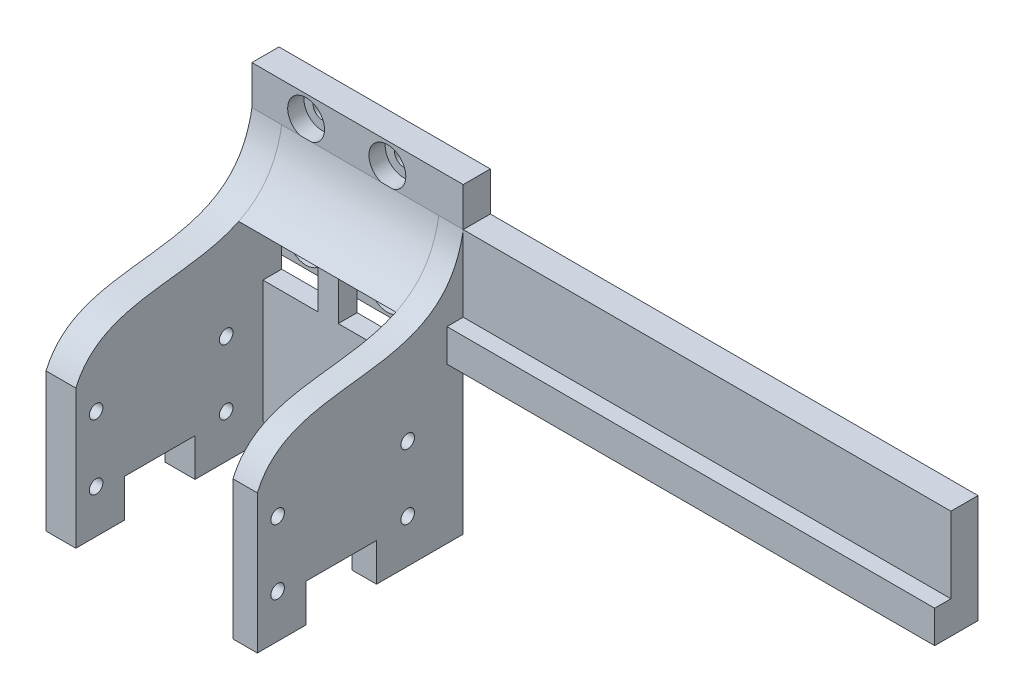
SolidWorks part; units mm, degrees
ref_plane "Front Plane" through (0, 0, 0) normal (0, 0, 1) x (1, 0, 0)
ref_plane "Top Plane" through (0, 0, 0) normal (0, 1, 0) x (1, 0, 0)
ref_plane "Right Plane" through (0, 0, 0) normal (1, 0, 0) x (0, 0, -1)
sketch "Sketch1" plane through (0, 0, 0) normal (0, 0, 1) x (1, 0, 0)
  line L0 (-17.7547, -9.0498) -> (-17.7547, -1.8498)
  line L1 (-56.7547, -1.8498) -> (-17.7547, -1.8498)
  line L2 (-56.7547, -1.8498) -> (-56.7547, -15.4856)
  line L3 (-17.7547, -29.0498) -> (72.2453, -29.0498)
  line L4 (72.2453, -9.0498) -> (72.2453, -29.0498)
  line L5 (-17.7547, -9.0498) -> (72.2453, -9.0498)
  line L8 (-56.7547, -15.4856) -> (-56.7547, -29.8498)
  line L9 (-56.7547, -29.8498) -> (-17.7547, -29.8498)
  line L10 (-17.7547, -29.0498) -> (-17.7547, -29.8498)
  point P0 (0, 0)
  dimension "D1" = 7.2
  dimension "D2" = 20
  dimension "D3" = 90
  dimension "D4" = 39
  dimension "D5" = 39
extrude "Boss-Extrude1" add sketch "Sketch1" along normal blind 5
sketch "Sketch2" plane through (0, 0, 5) normal (0, 0, 1) x (1, 0, 0)
  line L0 (-46.7547, -5.8498) -> (-46.7547, -25.8498) construction
  line L1 (-46.7547, -25.8498) -> (-31.7547, -25.8498) construction
  line L2 (-31.7547, -25.8498) -> (-31.7547, -5.8498) construction
  line L3 (-31.7547, -5.8498) -> (-46.7547, -5.8498) construction
  line L4 (-56.7547, -29.8498) -> (-17.7547, -29.8498) construction
  line L5 (-56.7547, -1.8498) -> (-56.7547, -29.8498) construction
  line L6 (-46.7547, -5.8498) -> (-31.7547, -25.8498) construction
  line L7 (-31.7547, -5.8498) -> (-46.7547, -25.8498) construction
  line L8 (-39.2547, -15.8498) -> (72.2453, -15.8498) construction
  line L9 (72.2453, -29.0498) -> (72.2453, -9.0498) construction
  line L10 (-17.7547, -1.8498) -> (-56.7547, -1.8498) construction
  circle A0 centre (-46.7547, -5.8498) radius 1.7
  circle A1 centre (-31.7547, -5.8498) radius 1.7
  circle A2 centre (-31.7547, -25.8498) radius 1.7
  circle A3 centre (-46.7547, -25.8498) radius 1.7
  point P12 (-37.2547, -29.8498)
  dimension "D1" = 3.4
  dimension "D2" = 15
  dimension "D3" = 20
  dimension "D4" = 15
  dimension "D5" = 20
  dimension "D6" = 4
  dimension "D7" = 10
  dimension "D8" = 14
extrude "Cut-Extrude1" cut sketch "Sketch2" against normal up to surface (5 mm away) contours A1 | A0 | A3 | A2 up to face at (-5.0047, -17.4498, 0)
sketch "Sketch3" plane through (0, 0, 5) normal (0, 0, 1) x (1, 0, 0)
  line L0 (-56.7547, -1.8498) -> (-56.7547, -29.8498) construction
  line L1 (-56.7547, -11.8498) -> (-51.2547, -11.8498)
  line L2 (-56.7547, -11.8498) -> (-56.7547, -57.7298)
  line L3 (-56.7547, -57.7298) -> (-51.2547, -57.7298)
  line L4 (-51.2547, -11.8498) -> (-51.2547, -57.7298)
  line L6 (-17.7547, -29.8498) -> (-17.7547, -29.0498) construction
  line L7 (-17.7547, -57.7298) -> (-22.2547, -57.7298)
  line L8 (-17.7547, -57.7298) -> (-17.7547, -11.8498)
  line L9 (-17.7547, -11.8498) -> (-22.2547, -11.8498)
  line L10 (-22.2547, -57.7298) -> (-22.2547, -11.8498)
  line L11 (-17.7547, -1.8498) -> (-56.7547, -1.8498) construction
  line L12 (-56.7547, -29.8498) -> (-17.7547, -29.8498) construction
  dimension "D1" = 27.88
  dimension "D2" = 27.88
  dimension "D3" = 29
  dimension "D4" = 4.5
  dimension "D5" = 0
  dimension "D6" = 0
  dimension "D7" = 10
extrude "Boss-Extrude2" add sketch "Sketch3" along normal blind 38
sketch "Sketch4" plane through (-56.7547, 0, 0) normal (-1, 0, 0) x (0, 0, 1)
  line L0 (5, -29.8498) -> (0, -29.8498) construction
  line L5 (34, -57.7298) -> (34, -50.7298)
  line L6 (34, -50.7298) -> (21, -50.7298)
  line L7 (21, -50.7298) -> (21, -57.7298)
  line L8 (15.25, -37.7298) -> (15.25, -49.7298) construction
  line L9 (15.25, -49.7298) -> (39.25, -49.7298) construction
  line L10 (39.25, -49.7298) -> (39.25, -37.7298) construction
  line L11 (43, -57.7298) -> (5, -57.7298) construction
  line L14 (2.5, -29.8498) -> (8, -29.8498)
  line L15 (2.5, -29.8498) -> (2.5, -61.3623)
  line L16 (2.5, -61.3623) -> (8, -61.3623)
  line L18 (21, -57.7298) -> (34, -57.7298)
  line L23 (39.25, -37.7298) -> (15.25, -37.7298) construction
  line L24 (8, -29.8498) -> (8, -61.3623)
  line L25 (5, -29.8498) -> (5, -57.7298) construction
  circle A0 centre (15.25, -37.7298) radius 1.25
  circle A1 centre (39.25, -37.7298) radius 1.25
  circle A2 centre (39.25, -49.7298) radius 1.25
  circle A3 centre (15.25, -49.7298) radius 1.25
  line M2 (0, -29.8498) -> (5, -29.8498)
  dimension "D1" = 12
  dimension "D6" = 2.5
  dimension "D3" = 24
  dimension "D4" = 7
  dimension "D5" = 13
  dimension "D7" = 8
  dimension "D8" = 3
  dimension "D9" = 7.25
  dimension "D10" = 13
  dimension "D2" = 0
extrude "Cut-Extrude2" cut sketch "Sketch4" against normal up to surface (39 mm away) contours A0 | A1 | A2 | L6 L7 L5 M2 | A3 region at (-56.7547, -54.2298, 27.5) region at (-56.7547, -37.7298, 15.25) region at (-56.7547, -37.7298, 39.25) region at (-56.7547, -49.7298, 39.25) region at (-56.7547, -49.7298, 15.25) up to face at (-17.7547, -32.1198, 13.25)
sketch "Sketch5" plane through (0, 0, 0) normal (0, 0, -1) x (-1, 0, 0)
  line L0 (-72.2453, -29.0498) -> (-7.1104, -29.0498) construction
  line L2 (-72.2453, -26.6698) -> (-71.8003, -26.6698) construction
  line L3 (-65.5853, -26.6698) -> (-65.1403, -26.6698)
  line L4 (-72.2453, -29.0498) -> (-72.2453, -9.0498) construction
  line L5 (-72.2453, -26.6698) -> (-71.8003, -26.6698)
  line L6 (-71.8003, -26.6698) -> (-70.9844, -28.9116)
  line L7 (-70.787, -29.0498) -> (-70.377, -29.0498)
  line L8 (-70.1797, -28.9116) -> (-69.3637, -26.6698)
  line L9 (-69.3637, -26.6698) -> (-68.4737, -26.6698)
  line L10 (-68.4737, -26.6698) -> (-67.6578, -28.9116)
  line L11 (-67.4604, -29.0498) -> (-67.0504, -29.0498)
  line L12 (-66.8531, -28.9116) -> (-66.0372, -26.6698)
  line L13 (-66.0372, -26.6698) -> (-65.5872, -26.6698)
  line L14 (-65.1403, -26.6698) -> (-64.3244, -28.9116)
  line L15 (-64.127, -29.0498) -> (-63.717, -29.0498)
  line L16 (-63.5197, -28.9116) -> (-62.7037, -26.6698)
  line L17 (-62.7037, -26.6698) -> (-61.8137, -26.6698)
  line L18 (-61.8137, -26.6698) -> (-60.9978, -28.9116)
  line L19 (-60.8004, -29.0498) -> (-60.3904, -29.0498)
  line L20 (-60.1931, -28.9116) -> (-59.3772, -26.6698)
  line L21 (-59.3772, -26.6698) -> (-58.9272, -26.6698)
  line L22 (-58.9253, -26.6698) -> (-58.4803, -26.6698)
  line L23 (-58.4803, -26.6698) -> (-57.6644, -28.9116)
  line L24 (-57.467, -29.0498) -> (-57.057, -29.0498)
  line L25 (-56.8597, -28.9116) -> (-56.0437, -26.6698)
  line L26 (-56.0437, -26.6698) -> (-55.1537, -26.6698)
  line L27 (-55.1537, -26.6698) -> (-54.3378, -28.9116)
  line L28 (-54.1404, -29.0498) -> (-53.7304, -29.0498)
  line L29 (-53.5331, -28.9116) -> (-52.7172, -26.6698)
  line L30 (-52.7172, -26.6698) -> (-52.2672, -26.6698)
  line L31 (-52.2653, -26.6698) -> (-51.8203, -26.6698)
  line L32 (-51.8203, -26.6698) -> (-51.0044, -28.9116)
  line L33 (-50.807, -29.0498) -> (-50.397, -29.0498)
  line L34 (-50.1997, -28.9116) -> (-49.3837, -26.6698)
  line L35 (-49.3837, -26.6698) -> (-48.4937, -26.6698)
  line L36 (-48.4937, -26.6698) -> (-47.6778, -28.9116)
  line L37 (-47.4804, -29.0498) -> (-47.0704, -29.0498)
  line L38 (-46.8731, -28.9116) -> (-46.0572, -26.6698)
  line L39 (-46.0572, -26.6698) -> (-45.6072, -26.6698)
  line L40 (-45.6053, -26.6698) -> (-45.1603, -26.6698)
  line L41 (-45.1603, -26.6698) -> (-44.3444, -28.9116)
  line L42 (-44.147, -29.0498) -> (-43.737, -29.0498)
  line L43 (-43.5397, -28.9116) -> (-42.7237, -26.6698)
  line L44 (-42.7237, -26.6698) -> (-41.8337, -26.6698)
  line L45 (-41.8337, -26.6698) -> (-41.0178, -28.9116)
  line L46 (-40.8204, -29.0498) -> (-40.4104, -29.0498)
  line L47 (-40.2131, -28.9116) -> (-39.3972, -26.6698)
  line L48 (-39.3972, -26.6698) -> (-38.9472, -26.6698)
  line L49 (-38.9453, -26.6698) -> (-38.5003, -26.6698)
  line L50 (-38.5003, -26.6698) -> (-37.6844, -28.9116)
  line L51 (-37.487, -29.0498) -> (-37.077, -29.0498)
  line L52 (-36.8797, -28.9116) -> (-36.0637, -26.6698)
  line L53 (-36.0637, -26.6698) -> (-35.1737, -26.6698)
  line L54 (-35.1737, -26.6698) -> (-34.3578, -28.9116)
  line L55 (-34.1604, -29.0498) -> (-33.7504, -29.0498)
  line L56 (-33.5531, -28.9116) -> (-32.7372, -26.6698)
  line L57 (-32.7372, -26.6698) -> (-32.2872, -26.6698)
  line L58 (-32.2853, -26.6698) -> (-31.8403, -26.6698)
  line L59 (-31.8403, -26.6698) -> (-31.0244, -28.9116)
  line L60 (-30.827, -29.0498) -> (-30.417, -29.0498)
  line L61 (-30.2197, -28.9116) -> (-29.4037, -26.6698)
  line L62 (-29.4037, -26.6698) -> (-28.5137, -26.6698)
  line L63 (-28.5137, -26.6698) -> (-27.6978, -28.9116)
  line L64 (-27.5004, -29.0498) -> (-27.0904, -29.0498)
  line L65 (-26.8931, -28.9116) -> (-26.0772, -26.6698)
  line L66 (-26.0772, -26.6698) -> (-25.6272, -26.6698)
  line L67 (-25.6253, -26.6698) -> (-25.1803, -26.6698)
  line L68 (-25.1803, -26.6698) -> (-24.3644, -28.9116)
  line L69 (-24.167, -29.0498) -> (-23.757, -29.0498)
  line L70 (-23.5597, -28.9116) -> (-22.7437, -26.6698)
  line L71 (-22.7437, -26.6698) -> (-21.8537, -26.6698)
  line L72 (-21.8537, -26.6698) -> (-21.0378, -28.9116)
  line L73 (-20.8404, -29.0498) -> (-20.4304, -29.0498)
  line L74 (-20.2331, -28.9116) -> (-19.4172, -26.6698)
  line L75 (-19.4172, -26.6698) -> (-18.9672, -26.6698)
  line L76 (-18.9653, -26.6698) -> (-18.5203, -26.6698)
  line L77 (-18.5203, -26.6698) -> (-17.7044, -28.9116)
  line L78 (-17.507, -29.0498) -> (-17.097, -29.0498)
  line L79 (-16.8997, -28.9116) -> (-16.0837, -26.6698)
  line L80 (-16.0837, -26.6698) -> (-15.1937, -26.6698)
  line L81 (-15.1937, -26.6698) -> (-14.3778, -28.9116)
  line L82 (-14.1804, -29.0498) -> (-13.7704, -29.0498)
  line L83 (-13.5731, -28.9116) -> (-12.7572, -26.6698)
  line L84 (-12.7572, -26.6698) -> (-12.3072, -26.6698)
  line L85 (-12.3053, -26.6698) -> (-11.8603, -26.6698)
  line L86 (-11.8603, -26.6698) -> (-11.0444, -28.9116)
  line L87 (-10.847, -29.0498) -> (-10.437, -29.0498)
  line L88 (-10.2397, -28.9116) -> (-9.4237, -26.6698)
  line L89 (-9.4237, -26.6698) -> (-8.5337, -26.6698)
  line L90 (-8.5337, -26.6698) -> (-7.7178, -28.9116)
  line L91 (-7.5204, -29.0498) -> (-7.1104, -29.0498)
  line L92 (-6.9131, -28.9116) -> (-6.0972, -26.6698)
  line L93 (-6.0972, -26.6698) -> (-5.6472, -26.6698)
  line L94 (-69.3637, -26.6698) -> (-68.4737, -26.6698) construction
  line L95 (-72.2453, -25.6698) -> (-5.6472, -25.6698)
  line L96 (-72.2453, -25.6698) -> (-72.2453, -26.6698)
  line L97 (-72.2453, -26.6698) -> (-71.8003, -26.6698)
  line L98 (-5.6472, -25.6698) -> (-5.6472, -26.6698)
  line L99 (-69.3637, -26.6698) -> (-68.4737, -26.6698)
  line L100 (-66.0372, -26.6698) -> (-65.1403, -26.6698) construction
  line L101 (-66.0372, -26.6698) -> (-65.1403, -26.6698)
  line L102 (-62.7037, -26.6698) -> (-61.8137, -26.6698)
  line L103 (-62.7037, -26.6698) -> (-61.8137, -26.6698) construction
  line L104 (-59.3772, -26.6698) -> (-58.4803, -26.6698)
  line L105 (-59.3772, -26.6698) -> (-58.4803, -26.6698) construction
  line L106 (-56.0437, -26.6698) -> (-55.1537, -26.6698)
  line L107 (-56.0437, -26.6698) -> (-55.1537, -26.6698) construction
  line L108 (-52.7172, -26.6698) -> (-51.8203, -26.6698)
  line L109 (-52.7172, -26.6698) -> (-51.8203, -26.6698) construction
  line L110 (-49.3837, -26.6698) -> (-48.4937, -26.6698) construction
  line L111 (-49.3837, -26.6698) -> (-48.4937, -26.6698)
  line L112 (-46.0572, -26.6698) -> (-45.1603, -26.6698) construction
  line L113 (-46.0572, -26.6698) -> (-45.1603, -26.6698)
  line L114 (-42.7237, -26.6698) -> (-41.8337, -26.6698) construction
  line L115 (-42.7237, -26.6698) -> (-41.8337, -26.6698)
  line L116 (-39.3972, -26.6698) -> (-38.5003, -26.6698) construction
  line L117 (-39.3972, -26.6698) -> (-38.5003, -26.6698)
  line L118 (-36.0637, -26.6698) -> (-35.1737, -26.6698) construction
  line L119 (-36.0637, -26.6698) -> (-35.1737, -26.6698)
  line L120 (-32.7372, -26.6698) -> (-31.8403, -26.6698) construction
  line L121 (-32.7372, -26.6698) -> (-31.8403, -26.6698)
  line L122 (-29.4037, -26.6698) -> (-28.5137, -26.6698) construction
  line L123 (-29.4037, -26.6698) -> (-28.5137, -26.6698)
  line L124 (-26.0772, -26.6698) -> (-25.1803, -26.6698) construction
  line L125 (-26.0772, -26.6698) -> (-25.1803, -26.6698)
  line L126 (-22.7437, -26.6698) -> (-21.8537, -26.6698)
  line L127 (-22.7437, -26.6698) -> (-21.8537, -26.6698) construction
  line L128 (-19.4172, -26.6698) -> (-18.5203, -26.6698)
  line L129 (-19.4172, -26.6698) -> (-18.5203, -26.6698) construction
  line L130 (-16.0837, -26.6698) -> (-15.1937, -26.6698)
  line L131 (-16.0837, -26.6698) -> (-15.1937, -26.6698) construction
  line L132 (-12.7572, -26.6698) -> (-11.8603, -26.6698)
  line L133 (-12.7572, -26.6698) -> (-11.8603, -26.6698) construction
  line L134 (-9.4237, -26.6698) -> (-8.5337, -26.6698)
  line L135 (-9.4237, -26.6698) -> (-8.5337, -26.6698) construction
  line L136 (-6.0972, -26.6698) -> (-5.6472, -26.6698)
  line L137 (-6.0972, -26.6698) -> (-5.6472, -26.6698) construction
  arc A0 (-70.377, -29.0498) -> (-70.1797, -28.9116) centre (-70.377, -28.8398) ccw
  arc A1 (-70.9844, -28.9116) -> (-70.787, -29.0498) centre (-70.787, -28.8398) ccw
  arc A2 (-67.6578, -28.9116) -> (-67.4604, -29.0498) centre (-67.4604, -28.8398) ccw
  arc A3 (-67.0504, -29.0498) -> (-66.8531, -28.9116) centre (-67.0504, -28.8398) ccw
  arc A4 (-63.717, -29.0498) -> (-63.5197, -28.9116) centre (-63.717, -28.8398) ccw
  arc A5 (-64.3244, -28.9116) -> (-64.127, -29.0498) centre (-64.127, -28.8398) ccw
  arc A6 (-60.9978, -28.9116) -> (-60.8004, -29.0498) centre (-60.8004, -28.8398) ccw
  arc A7 (-60.3904, -29.0498) -> (-60.1931, -28.9116) centre (-60.3904, -28.8398) ccw
  arc A8 (-57.057, -29.0498) -> (-56.8597, -28.9116) centre (-57.057, -28.8398) ccw
  arc A9 (-57.6644, -28.9116) -> (-57.467, -29.0498) centre (-57.467, -28.8398) ccw
  arc A10 (-54.3378, -28.9116) -> (-54.1404, -29.0498) centre (-54.1404, -28.8398) ccw
  arc A11 (-53.7304, -29.0498) -> (-53.5331, -28.9116) centre (-53.7304, -28.8398) ccw
  arc A12 (-50.397, -29.0498) -> (-50.1997, -28.9116) centre (-50.397, -28.8398) ccw
  arc A13 (-51.0044, -28.9116) -> (-50.807, -29.0498) centre (-50.807, -28.8398) ccw
  arc A14 (-47.6778, -28.9116) -> (-47.4804, -29.0498) centre (-47.4804, -28.8398) ccw
  arc A15 (-47.0704, -29.0498) -> (-46.8731, -28.9116) centre (-47.0704, -28.8398) ccw
  arc A16 (-43.737, -29.0498) -> (-43.5397, -28.9116) centre (-43.737, -28.8398) ccw
  arc A17 (-44.3444, -28.9116) -> (-44.147, -29.0498) centre (-44.147, -28.8398) ccw
  arc A18 (-41.0178, -28.9116) -> (-40.8204, -29.0498) centre (-40.8204, -28.8398) ccw
  arc A19 (-40.4104, -29.0498) -> (-40.2131, -28.9116) centre (-40.4104, -28.8398) ccw
  arc A20 (-37.077, -29.0498) -> (-36.8797, -28.9116) centre (-37.077, -28.8398) ccw
  arc A21 (-37.6844, -28.9116) -> (-37.487, -29.0498) centre (-37.487, -28.8398) ccw
  arc A22 (-34.3578, -28.9116) -> (-34.1604, -29.0498) centre (-34.1604, -28.8398) ccw
  arc A23 (-33.7504, -29.0498) -> (-33.5531, -28.9116) centre (-33.7504, -28.8398) ccw
  arc A24 (-30.417, -29.0498) -> (-30.2197, -28.9116) centre (-30.417, -28.8398) ccw
  arc A25 (-31.0244, -28.9116) -> (-30.827, -29.0498) centre (-30.827, -28.8398) ccw
  arc A26 (-27.6978, -28.9116) -> (-27.5004, -29.0498) centre (-27.5004, -28.8398) ccw
  arc A27 (-27.0904, -29.0498) -> (-26.8931, -28.9116) centre (-27.0904, -28.8398) ccw
  arc A28 (-23.757, -29.0498) -> (-23.5597, -28.9116) centre (-23.757, -28.8398) ccw
  arc A29 (-24.3644, -28.9116) -> (-24.167, -29.0498) centre (-24.167, -28.8398) ccw
  arc A30 (-21.0378, -28.9116) -> (-20.8404, -29.0498) centre (-20.8404, -28.8398) ccw
  arc A31 (-20.4304, -29.0498) -> (-20.2331, -28.9116) centre (-20.4304, -28.8398) ccw
  arc A32 (-17.097, -29.0498) -> (-16.8997, -28.9116) centre (-17.097, -28.8398) ccw
  arc A33 (-17.7044, -28.9116) -> (-17.507, -29.0498) centre (-17.507, -28.8398) ccw
  arc A34 (-14.3778, -28.9116) -> (-14.1804, -29.0498) centre (-14.1804, -28.8398) ccw
  arc A35 (-13.7704, -29.0498) -> (-13.5731, -28.9116) centre (-13.7704, -28.8398) ccw
  arc A36 (-10.437, -29.0498) -> (-10.2397, -28.9116) centre (-10.437, -28.8398) ccw
  arc A37 (-11.0444, -28.9116) -> (-10.847, -29.0498) centre (-10.847, -28.8398) ccw
  arc A38 (-7.7178, -28.9116) -> (-7.5204, -29.0498) centre (-7.5204, -28.8398) ccw
  arc A39 (-7.1104, -29.0498) -> (-6.9131, -28.9116) centre (-7.1104, -28.8398) ccw
  point P16 (-70.23, -29.0498)
  point P19 (-70.9341, -29.0498)
  point P23 (-67.6075, -29.0498)
  point P28 (-66.9034, -29.0498)
  line M7 (-72.2453, -9.0498) -> (-72.2453, -29.0498)
  line M8 (-72.2453, -29.0498) -> (17.7547, -29.0498)
  dimension "D4" = 0.21
  dimension "D7" = 110
  dimension "D2" = 0.445
  dimension "D5" = 0.21
  dimension "D10" = 0.21
  dimension "D12" = 0.21
  dimension "D1" = 2.38
  dimension "D3" = 0.89
  dimension "D6" = 0.41
  dimension "D8" = 110
  dimension "D9" = 110
  dimension "D11" = 0.41
  dimension "D13" = 0.45
  dimension "D14" = 110
  dimension "D15" = 10
  dimension "D16" = 1
extrude "Boss-Extrude3" add sketch "Sketch5" along normal blind 1 contours L91 A39 L92 L93 L98 L95 L5 L6 A1 A0 L8 L9 L10 A2 A3 L12 L13 L101 L3 L14 A5 A4 L16 L17 L18 A6 A7 L20 L21 L104 L22 L23 A9 A8 L25 L26 L27 A10 A11 L29 L30 L108 L31 L32 M7 M8 region at (65.5862, -26.0029, 0)
sketch "Sketch7" plane through (0, 0, -1) normal (0, 0, -1) x (-1, 0, 0)
  line L5 (-20.8404, -29.0498) -> (-23.757, -29.0498) construction
  line L6 (-72.2453, -23.0498) -> (17.7547, -23.0498)
  line L7 (-72.2453, -23.0498) -> (-72.2453, -29.0498)
  line L8 (-72.2453, -29.0498) -> (17.7547, -29.0498)
  line L9 (17.7547, -23.0498) -> (17.7547, -29.0498)
  line L10 (-72.2453, -25.6698) -> (-72.2453, -9.0498) construction
  line L11 (17.7547, -11.8498) -> (17.7547, -29.0498) construction
  dimension "D1" = 0
  dimension "D2" = 0
  dimension "D3" = 0
  dimension "D4" = 6
extrude "Boss-Extrude4" add sketch "Sketch7" against normal blind 3 from surface contours L6 L9 L8 L7 starting at face at (-30.0547, -25.8498, 5)
sketch "Sketch8" plane through (0, 0, -1) normal (0, 0, -1) x (-1, 0, 0)
  line L0 (-72.2453, -26.6698) -> (-72.2453, -29.0498)
  line L1 (-72.2453, -29.0498) -> (-70.787, -29.0498)
  line L2 (-70.377, -29.0498) -> (-67.4604, -29.0498)
  line L3 (-67.0504, -29.0498) -> (-64.127, -29.0498)
  line L4 (-63.717, -29.0498) -> (-60.8004, -29.0498)
  line L5 (-60.3904, -29.0498) -> (-57.467, -29.0498)
  line L6 (-57.057, -29.0498) -> (-54.1404, -29.0498)
  line L7 (-53.7304, -29.0498) -> (-50.807, -29.0498)
  line L8 (-50.397, -29.0498) -> (-47.4804, -29.0498)
  line L9 (-47.0704, -29.0498) -> (-44.147, -29.0498)
  line L10 (-43.737, -29.0498) -> (-40.8204, -29.0498)
  line L11 (-40.4104, -29.0498) -> (-37.487, -29.0498)
  line L12 (-37.077, -29.0498) -> (-34.1604, -29.0498)
  line L13 (-33.7504, -29.0498) -> (-30.827, -29.0498)
  line L14 (-30.417, -29.0498) -> (-27.5004, -29.0498)
  line L15 (-27.0904, -29.0498) -> (-24.167, -29.0498)
  line L16 (-23.757, -29.0498) -> (-20.8404, -29.0498)
  line L17 (-20.4304, -29.0498) -> (-17.507, -29.0498)
  line L18 (-17.097, -29.0498) -> (-14.1804, -29.0498)
  line L19 (-13.7704, -29.0498) -> (-10.847, -29.0498)
  line L20 (-7.3154, -29.0498) -> (-7.3154, -29.607) construction
  line L21 (-10.642, -29.0498) -> (-10.642, -29.5206) construction
  line L22 (-3.777, -29.0498) -> (-0.8604, -29.0498)
  line L23 (-7.312, -29.0498) -> (-7.107, -29.0498)
  line L24 (-6.9097, -28.9116) -> (-6.0937, -26.6698)
  line L25 (-0.6554, -29.0498) -> (-0.652, -29.0498)
  line L26 (-5.2037, -26.6698) -> (-4.3878, -28.9116)
  line L27 (-6.0937, -26.6698) -> (-5.2037, -26.6698)
  line L28 (-0.447, -29.0498) -> (2.4696, -29.0498)
  line L29 (-3.5797, -28.9116) -> (-2.7637, -26.6698)
  line L31 (-1.8737, -26.6698) -> (-1.0578, -28.9116)
  line L32 (-2.7637, -26.6698) -> (-1.8737, -26.6698)
  line L34 (-0.2497, -28.9116) -> (0.5663, -26.6698)
  line L36 (1.4563, -26.6698) -> (2.2722, -28.9116)
  line L37 (0.5663, -26.6698) -> (1.4563, -26.6698)
  line L39 (3.0803, -28.9116) -> (3.8963, -26.6698)
  line L40 (2.883, -29.0498) -> (5.7996, -29.0498)
  line L41 (4.7863, -26.6698) -> (5.6022, -28.9116)
  line L42 (3.8963, -26.6698) -> (4.7863, -26.6698)
  line L44 (6.4103, -28.9116) -> (7.2263, -26.6698)
  line L45 (6.213, -29.0498) -> (9.1296, -29.0498)
  line L46 (8.1163, -26.6698) -> (8.9322, -28.9116)
  line L47 (7.2263, -26.6698) -> (8.1163, -26.6698)
  line L49 (9.7403, -28.9116) -> (10.5563, -26.6698)
  line L50 (9.543, -29.0498) -> (12.4596, -29.0498)
  line L51 (11.4463, -26.6698) -> (12.2622, -28.9116)
  line L52 (10.5563, -26.6698) -> (11.4463, -26.6698)
  line L54 (13.0703, -28.9116) -> (13.8863, -26.6698)
  line L55 (12.873, -29.0498) -> (15.7896, -29.0498)
  line L56 (14.7763, -26.6698) -> (15.5922, -28.9116)
  line L57 (13.8863, -26.6698) -> (14.7763, -26.6698)
  line L58 (-10.847, -29.0498) -> (-10.642, -29.0498)
  line L59 (-10.437, -29.0498) -> (-7.5204, -29.0498)
  line L60 (-7.107, -29.0498) -> (-4.1904, -29.0498)
  line L78 (-5.6472, -25.6698) -> (-72.2453, -25.6698)
  line L79 (-72.2453, -25.6698) -> (-72.2453, -26.6698)
  line L80 (-72.2453, -26.6698) -> (-71.8003, -26.6698)
  line L81 (-71.8003, -26.6698) -> (-70.9844, -28.9116)
  line L82 (-70.787, -29.0498) -> (-70.377, -29.0498)
  line L83 (-70.1797, -28.9116) -> (-69.3637, -26.6698)
  line L84 (-69.3637, -26.6698) -> (-68.4737, -26.6698)
  line L85 (-68.4737, -26.6698) -> (-67.6578, -28.9116)
  line L86 (-67.4604, -29.0498) -> (-67.0504, -29.0498)
  line L87 (-66.8531, -28.9116) -> (-66.0372, -26.6698)
  line L88 (-66.0372, -26.6698) -> (-65.1403, -26.6698)
  line L89 (-65.1403, -26.6698) -> (-64.3244, -28.9116)
  line L90 (-64.127, -29.0498) -> (-63.717, -29.0498)
  line L91 (-63.5197, -28.9116) -> (-62.7037, -26.6698)
  line L92 (-62.7037, -26.6698) -> (-61.8137, -26.6698)
  line L93 (-61.8137, -26.6698) -> (-60.9978, -28.9116)
  line L94 (-60.8004, -29.0498) -> (-60.3904, -29.0498)
  line L95 (-60.1931, -28.9116) -> (-59.3772, -26.6698)
  line L96 (-59.3772, -26.6698) -> (-58.4803, -26.6698)
  line L97 (-58.4803, -26.6698) -> (-57.6644, -28.9116)
  line L98 (-57.467, -29.0498) -> (-57.057, -29.0498)
  line L99 (-56.8597, -28.9116) -> (-56.0437, -26.6698)
  line L100 (-56.0437, -26.6698) -> (-55.1537, -26.6698)
  line L101 (-55.1537, -26.6698) -> (-54.3378, -28.9116)
  line L102 (-54.1404, -29.0498) -> (-53.7304, -29.0498)
  line L103 (-53.5331, -28.9116) -> (-52.7172, -26.6698)
  line L104 (-52.7172, -26.6698) -> (-51.8203, -26.6698)
  line L105 (-51.8203, -26.6698) -> (-51.0044, -28.9116)
  line L106 (-50.807, -29.0498) -> (-50.397, -29.0498)
  line L107 (-50.1997, -28.9116) -> (-49.3837, -26.6698)
  line L108 (-49.3837, -26.6698) -> (-48.4937, -26.6698)
  line L109 (-48.4937, -26.6698) -> (-47.6778, -28.9116)
  line L110 (-47.4804, -29.0498) -> (-47.0704, -29.0498)
  line L111 (-46.8731, -28.9116) -> (-46.0572, -26.6698)
  line L112 (-46.0572, -26.6698) -> (-45.1603, -26.6698)
  line L113 (-45.1603, -26.6698) -> (-44.3444, -28.9116)
  line L114 (-44.147, -29.0498) -> (-43.737, -29.0498)
  line L115 (-43.5397, -28.9116) -> (-42.7237, -26.6698)
  line L116 (-42.7237, -26.6698) -> (-41.8337, -26.6698)
  line L117 (-41.8337, -26.6698) -> (-41.0178, -28.9116)
  line L118 (-40.8204, -29.0498) -> (-40.4104, -29.0498)
  line L119 (-40.2131, -28.9116) -> (-39.3972, -26.6698)
  line L120 (-39.3972, -26.6698) -> (-38.5003, -26.6698)
  line L121 (-38.5003, -26.6698) -> (-37.6844, -28.9116)
  line L122 (-37.487, -29.0498) -> (-37.077, -29.0498)
  line L123 (-36.8797, -28.9116) -> (-36.0637, -26.6698)
  line L124 (-36.0637, -26.6698) -> (-35.1737, -26.6698)
  line L125 (-35.1737, -26.6698) -> (-34.3578, -28.9116)
  line L126 (-34.1604, -29.0498) -> (-33.7504, -29.0498)
  line L127 (-33.5531, -28.9116) -> (-32.7372, -26.6698)
  line L128 (-32.7372, -26.6698) -> (-31.8403, -26.6698)
  line L129 (-31.8403, -26.6698) -> (-31.0244, -28.9116)
  line L130 (-30.827, -29.0498) -> (-30.417, -29.0498)
  line L131 (-30.2197, -28.9116) -> (-29.4037, -26.6698)
  line L132 (-29.4037, -26.6698) -> (-28.5137, -26.6698)
  line L133 (-28.5137, -26.6698) -> (-27.6978, -28.9116)
  line L134 (-27.5004, -29.0498) -> (-27.0904, -29.0498)
  line L135 (-26.8931, -28.9116) -> (-26.0772, -26.6698)
  line L136 (-26.0772, -26.6698) -> (-25.1803, -26.6698)
  line L137 (-25.1803, -26.6698) -> (-24.3644, -28.9116)
  line L138 (-24.167, -29.0498) -> (-23.757, -29.0498)
  line L139 (-23.5597, -28.9116) -> (-22.7437, -26.6698)
  line L140 (-22.7437, -26.6698) -> (-21.8537, -26.6698)
  line L141 (-21.8537, -26.6698) -> (-21.0378, -28.9116)
  line L142 (-20.8404, -29.0498) -> (-20.4304, -29.0498)
  line L143 (-20.2331, -28.9116) -> (-19.4172, -26.6698)
  line L144 (-19.4172, -26.6698) -> (-18.5203, -26.6698)
  line L145 (-18.5203, -26.6698) -> (-17.7044, -28.9116)
  line L146 (-17.507, -29.0498) -> (-17.097, -29.0498)
  line L147 (-16.8997, -28.9116) -> (-16.0837, -26.6698)
  line L148 (-16.0837, -26.6698) -> (-15.1937, -26.6698)
  line L149 (-15.1937, -26.6698) -> (-14.3778, -28.9116)
  line L150 (-14.1804, -29.0498) -> (-13.7704, -29.0498)
  line L151 (-13.5731, -28.9116) -> (-12.7572, -26.6698)
  line L152 (-12.7572, -26.6698) -> (-11.8603, -26.6698)
  line L153 (-11.8603, -26.6698) -> (-11.0444, -28.9116)
  line L157 (-72.2453, -26.6698) -> (-71.8003, -26.6698)
  line L158 (-71.8003, -26.6698) -> (-70.9844, -28.9116)
  line L160 (-70.1797, -28.9116) -> (-69.3637, -26.6698)
  line L161 (-69.3637, -26.6698) -> (-68.4737, -26.6698)
  line L162 (-68.4737, -26.6698) -> (-67.6578, -28.9116)
  line L164 (-66.8531, -28.9116) -> (-66.0372, -26.6698)
  line L165 (-66.0372, -26.6698) -> (-65.1403, -26.6698)
  line L166 (-65.1403, -26.6698) -> (-64.3244, -28.9116)
  line L168 (-63.5197, -28.9116) -> (-62.7037, -26.6698)
  line L169 (-62.7037, -26.6698) -> (-61.8137, -26.6698)
  line L170 (-61.8137, -26.6698) -> (-60.9978, -28.9116)
  line L172 (-60.1931, -28.9116) -> (-59.3772, -26.6698)
  line L173 (-59.3772, -26.6698) -> (-58.4803, -26.6698)
  line L174 (-58.4803, -26.6698) -> (-57.6644, -28.9116)
  line L176 (-56.8597, -28.9116) -> (-56.0437, -26.6698)
  line L177 (-56.0437, -26.6698) -> (-55.1537, -26.6698)
  line L178 (-55.1537, -26.6698) -> (-54.3378, -28.9116)
  line L180 (-53.5331, -28.9116) -> (-52.7172, -26.6698)
  line L181 (-52.7172, -26.6698) -> (-51.8203, -26.6698)
  line L182 (-51.8203, -26.6698) -> (-51.0044, -28.9116)
  line L184 (-50.1997, -28.9116) -> (-49.3837, -26.6698)
  line L185 (-49.3837, -26.6698) -> (-48.4937, -26.6698)
  line L186 (-48.4937, -26.6698) -> (-47.6778, -28.9116)
  line L188 (-46.8731, -28.9116) -> (-46.0572, -26.6698)
  line L189 (-46.0572, -26.6698) -> (-45.1603, -26.6698)
  line L190 (-45.1603, -26.6698) -> (-44.3444, -28.9116)
  line L192 (-43.5397, -28.9116) -> (-42.7237, -26.6698)
  line L193 (-42.7237, -26.6698) -> (-41.8337, -26.6698)
  line L194 (-41.8337, -26.6698) -> (-41.0178, -28.9116)
  line L196 (-40.2131, -28.9116) -> (-39.3972, -26.6698)
  line L197 (-39.3972, -26.6698) -> (-38.5003, -26.6698)
  line L198 (-38.5003, -26.6698) -> (-37.6844, -28.9116)
  line L200 (-36.8797, -28.9116) -> (-36.0637, -26.6698)
  line L201 (-36.0637, -26.6698) -> (-35.1737, -26.6698)
  line L202 (-35.1737, -26.6698) -> (-34.3578, -28.9116)
  line L204 (-33.5531, -28.9116) -> (-32.7372, -26.6698)
  line L205 (-32.7372, -26.6698) -> (-31.8403, -26.6698)
  line L206 (-31.8403, -26.6698) -> (-31.0244, -28.9116)
  line L208 (-30.2197, -28.9116) -> (-29.4037, -26.6698)
  line L209 (-29.4037, -26.6698) -> (-28.5137, -26.6698)
  line L210 (-28.5137, -26.6698) -> (-27.6978, -28.9116)
  line L212 (-26.8931, -28.9116) -> (-26.0772, -26.6698)
  line L213 (-26.0772, -26.6698) -> (-25.1803, -26.6698)
  line L214 (-25.1803, -26.6698) -> (-24.3644, -28.9116)
  line L216 (-23.5597, -28.9116) -> (-22.7437, -26.6698)
  line L217 (-22.7437, -26.6698) -> (-21.8537, -26.6698)
  line L218 (-21.8537, -26.6698) -> (-21.0378, -28.9116)
  line L220 (-20.2331, -28.9116) -> (-19.4172, -26.6698)
  line L221 (-19.4172, -26.6698) -> (-18.5203, -26.6698)
  line L222 (-18.5203, -26.6698) -> (-17.7044, -28.9116)
  line L224 (-16.8997, -28.9116) -> (-16.0837, -26.6698)
  line L225 (-16.0837, -26.6698) -> (-15.1937, -26.6698)
  line L226 (-15.1937, -26.6698) -> (-14.3778, -28.9116)
  line L228 (-13.5731, -28.9116) -> (-12.7572, -26.6698)
  line L229 (-12.7572, -26.6698) -> (-11.8603, -26.6698)
  line L230 (-11.8603, -26.6698) -> (-11.0444, -28.9116)
  line L258 (-7.5204, -29.0498) -> (-7.1104, -29.0498)
  line L260 (-6.9131, -28.9116) -> (-6.0972, -26.6698)
  line L262 (-6.0972, -26.6698) -> (-5.6472, -26.6698)
  line L264 (-5.6472, -26.6698) -> (-5.6472, -25.6698)
  line L266 (-10.847, -29.0498) -> (-10.437, -29.0498)
  line L268 (-10.2397, -28.9116) -> (-9.4237, -26.6698)
  line L269 (-10.2397, -28.9116) -> (-9.4237, -26.6698)
  line L270 (-9.4237, -26.6698) -> (-8.5337, -26.6698)
  line L271 (-9.4237, -26.6698) -> (-8.5337, -26.6698)
  line L272 (-8.5337, -26.6698) -> (-7.7178, -28.9116)
  line L273 (-8.5337, -26.6698) -> (-7.7178, -28.9116)
  arc A0 (-7.107, -29.0498) -> (-6.9097, -28.9116) centre (-7.107, -28.8398) ccw
  arc A1 (-4.3878, -28.9116) -> (-4.1904, -29.0498) centre (-4.1904, -28.8398) ccw
  arc A2 (-3.777, -29.0498) -> (-3.5797, -28.9116) centre (-3.777, -28.8398) ccw
  arc A3 (-1.0578, -28.9116) -> (-0.8604, -29.0498) centre (-0.8604, -28.8398) ccw
  arc A4 (-0.447, -29.0498) -> (-0.2497, -28.9116) centre (-0.447, -28.8398) ccw
  arc A5 (2.2722, -28.9116) -> (2.4696, -29.0498) centre (2.4696, -28.8398) ccw
  arc A6 (2.883, -29.0498) -> (3.0803, -28.9116) centre (2.883, -28.8398) ccw
  arc A7 (5.6022, -28.9116) -> (5.7996, -29.0498) centre (5.7996, -28.8398) ccw
  arc A8 (6.213, -29.0498) -> (6.4103, -28.9116) centre (6.213, -28.8398) ccw
  arc A9 (8.9322, -28.9116) -> (9.1296, -29.0498) centre (9.1296, -28.8398) ccw
  arc A10 (9.543, -29.0498) -> (9.7403, -28.9116) centre (9.543, -28.8398) ccw
  arc A11 (12.2622, -28.9116) -> (12.4596, -29.0498) centre (12.4596, -28.8398) ccw
  arc A12 (12.873, -29.0498) -> (13.0703, -28.9116) centre (12.873, -28.8398) ccw
  arc A13 (15.5922, -28.9116) -> (15.7896, -29.0498) centre (15.7896, -28.8398) ccw
  arc A37 (-70.9844, -28.9116) -> (-70.787, -29.0498) centre (-70.787, -28.8398) ccw
  arc A38 (-70.377, -29.0498) -> (-70.1797, -28.9116) centre (-70.377, -28.8398) ccw
  arc A39 (-67.6578, -28.9116) -> (-67.4604, -29.0498) centre (-67.4604, -28.8398) ccw
  arc A40 (-67.0504, -29.0498) -> (-66.8531, -28.9116) centre (-67.0504, -28.8398) ccw
  arc A41 (-64.3244, -28.9116) -> (-64.127, -29.0498) centre (-64.127, -28.8398) ccw
  arc A42 (-63.717, -29.0498) -> (-63.5197, -28.9116) centre (-63.717, -28.8398) ccw
  arc A43 (-60.9978, -28.9116) -> (-60.8004, -29.0498) centre (-60.8004, -28.8398) ccw
  arc A44 (-60.3904, -29.0498) -> (-60.1931, -28.9116) centre (-60.3904, -28.8398) ccw
  arc A45 (-57.6644, -28.9116) -> (-57.467, -29.0498) centre (-57.467, -28.8398) ccw
  arc A46 (-57.057, -29.0498) -> (-56.8597, -28.9116) centre (-57.057, -28.8398) ccw
  arc A47 (-54.3378, -28.9116) -> (-54.1404, -29.0498) centre (-54.1404, -28.8398) ccw
  arc A48 (-53.7304, -29.0498) -> (-53.5331, -28.9116) centre (-53.7304, -28.8398) ccw
  arc A49 (-51.0044, -28.9116) -> (-50.807, -29.0498) centre (-50.807, -28.8398) ccw
  arc A50 (-50.397, -29.0498) -> (-50.1997, -28.9116) centre (-50.397, -28.8398) ccw
  arc A51 (-47.6778, -28.9116) -> (-47.4804, -29.0498) centre (-47.4804, -28.8398) ccw
  arc A52 (-47.0704, -29.0498) -> (-46.8731, -28.9116) centre (-47.0704, -28.8398) ccw
  arc A53 (-44.3444, -28.9116) -> (-44.147, -29.0498) centre (-44.147, -28.8398) ccw
  arc A54 (-43.737, -29.0498) -> (-43.5397, -28.9116) centre (-43.737, -28.8398) ccw
  arc A55 (-41.0178, -28.9116) -> (-40.8204, -29.0498) centre (-40.8204, -28.8398) ccw
  arc A56 (-40.4104, -29.0498) -> (-40.2131, -28.9116) centre (-40.4104, -28.8398) ccw
  arc A57 (-37.6844, -28.9116) -> (-37.487, -29.0498) centre (-37.487, -28.8398) ccw
  arc A58 (-37.077, -29.0498) -> (-36.8797, -28.9116) centre (-37.077, -28.8398) ccw
  arc A59 (-34.3578, -28.9116) -> (-34.1604, -29.0498) centre (-34.1604, -28.8398) ccw
  arc A60 (-33.7504, -29.0498) -> (-33.5531, -28.9116) centre (-33.7504, -28.8398) ccw
  arc A61 (-31.0244, -28.9116) -> (-30.827, -29.0498) centre (-30.827, -28.8398) ccw
  arc A62 (-30.417, -29.0498) -> (-30.2197, -28.9116) centre (-30.417, -28.8398) ccw
  arc A63 (-27.6978, -28.9116) -> (-27.5004, -29.0498) centre (-27.5004, -28.8398) ccw
  arc A64 (-27.0904, -29.0498) -> (-26.8931, -28.9116) centre (-27.0904, -28.8398) ccw
  arc A65 (-24.3644, -28.9116) -> (-24.167, -29.0498) centre (-24.167, -28.8398) ccw
  arc A66 (-23.757, -29.0498) -> (-23.5597, -28.9116) centre (-23.757, -28.8398) ccw
  arc A67 (-21.0378, -28.9116) -> (-20.8404, -29.0498) centre (-20.8404, -28.8398) ccw
  arc A68 (-20.4304, -29.0498) -> (-20.2331, -28.9116) centre (-20.4304, -28.8398) ccw
  arc A69 (-17.7044, -28.9116) -> (-17.507, -29.0498) centre (-17.507, -28.8398) ccw
  arc A70 (-17.097, -29.0498) -> (-16.8997, -28.9116) centre (-17.097, -28.8398) ccw
  arc A71 (-14.3778, -28.9116) -> (-14.1804, -29.0498) centre (-14.1804, -28.8398) ccw
  arc A72 (-13.7704, -29.0498) -> (-13.5731, -28.9116) centre (-13.7704, -28.8398) ccw
  arc A73 (-11.0444, -28.9116) -> (-10.847, -29.0498) centre (-10.847, -28.8398) ccw
  arc A74 (-70.9844, -28.9116) -> (-70.787, -29.0498) centre (-70.787, -28.8398) ccw
  arc A75 (-70.377, -29.0498) -> (-70.1797, -28.9116) centre (-70.377, -28.8398) ccw
  arc A76 (-67.6578, -28.9116) -> (-67.4604, -29.0498) centre (-67.4604, -28.8398) ccw
  arc A77 (-67.0504, -29.0498) -> (-66.8531, -28.9116) centre (-67.0504, -28.8398) ccw
  arc A78 (-64.3244, -28.9116) -> (-64.127, -29.0498) centre (-64.127, -28.8398) ccw
  arc A79 (-63.717, -29.0498) -> (-63.5197, -28.9116) centre (-63.717, -28.8398) ccw
  arc A80 (-60.9978, -28.9116) -> (-60.8004, -29.0498) centre (-60.8004, -28.8398) ccw
  arc A81 (-60.3904, -29.0498) -> (-60.1931, -28.9116) centre (-60.3904, -28.8398) ccw
  arc A82 (-57.6644, -28.9116) -> (-57.467, -29.0498) centre (-57.467, -28.8398) ccw
  arc A83 (-57.057, -29.0498) -> (-56.8597, -28.9116) centre (-57.057, -28.8398) ccw
  arc A84 (-54.3378, -28.9116) -> (-54.1404, -29.0498) centre (-54.1404, -28.8398) ccw
  arc A85 (-53.7304, -29.0498) -> (-53.5331, -28.9116) centre (-53.7304, -28.8398) ccw
  arc A86 (-51.0044, -28.9116) -> (-50.807, -29.0498) centre (-50.807, -28.8398) ccw
  arc A87 (-50.397, -29.0498) -> (-50.1997, -28.9116) centre (-50.397, -28.8398) ccw
  arc A88 (-47.6778, -28.9116) -> (-47.4804, -29.0498) centre (-47.4804, -28.8398) ccw
  arc A89 (-47.0704, -29.0498) -> (-46.8731, -28.9116) centre (-47.0704, -28.8398) ccw
  arc A90 (-44.3444, -28.9116) -> (-44.147, -29.0498) centre (-44.147, -28.8398) ccw
  arc A91 (-43.737, -29.0498) -> (-43.5397, -28.9116) centre (-43.737, -28.8398) ccw
  arc A92 (-41.0178, -28.9116) -> (-40.8204, -29.0498) centre (-40.8204, -28.8398) ccw
  arc A93 (-40.4104, -29.0498) -> (-40.2131, -28.9116) centre (-40.4104, -28.8398) ccw
  arc A94 (-37.6844, -28.9116) -> (-37.487, -29.0498) centre (-37.487, -28.8398) ccw
  arc A95 (-37.077, -29.0498) -> (-36.8797, -28.9116) centre (-37.077, -28.8398) ccw
  arc A96 (-34.3578, -28.9116) -> (-34.1604, -29.0498) centre (-34.1604, -28.8398) ccw
  arc A97 (-33.7504, -29.0498) -> (-33.5531, -28.9116) centre (-33.7504, -28.8398) ccw
  arc A98 (-31.0244, -28.9116) -> (-30.827, -29.0498) centre (-30.827, -28.8398) ccw
  arc A99 (-30.417, -29.0498) -> (-30.2197, -28.9116) centre (-30.417, -28.8398) ccw
  arc A100 (-27.6978, -28.9116) -> (-27.5004, -29.0498) centre (-27.5004, -28.8398) ccw
  arc A101 (-27.0904, -29.0498) -> (-26.8931, -28.9116) centre (-27.0904, -28.8398) ccw
  arc A102 (-24.3644, -28.9116) -> (-24.167, -29.0498) centre (-24.167, -28.8398) ccw
  arc A103 (-23.757, -29.0498) -> (-23.5597, -28.9116) centre (-23.757, -28.8398) ccw
  arc A104 (-21.0378, -28.9116) -> (-20.8404, -29.0498) centre (-20.8404, -28.8398) ccw
  arc A105 (-20.4304, -29.0498) -> (-20.2331, -28.9116) centre (-20.4304, -28.8398) ccw
  arc A106 (-17.7044, -28.9116) -> (-17.507, -29.0498) centre (-17.507, -28.8398) ccw
  arc A107 (-17.097, -29.0498) -> (-16.8997, -28.9116) centre (-17.097, -28.8398) ccw
  arc A108 (-14.3778, -28.9116) -> (-14.1804, -29.0498) centre (-14.1804, -28.8398) ccw
  arc A109 (-13.7704, -29.0498) -> (-13.5731, -28.9116) centre (-13.7704, -28.8398) ccw
  arc A110 (-11.0444, -28.9116) -> (-10.847, -29.0498) centre (-10.847, -28.8398) ccw
  arc A114 (-7.1104, -29.0498) -> (-6.9131, -28.9116) centre (-7.1104, -28.8398) ccw
  arc A116 (-10.437, -29.0498) -> (-10.2397, -28.9116) centre (-10.437, -28.8398) ccw
  arc A117 (-10.437, -29.0498) -> (-10.2397, -28.9116) centre (-10.437, -28.8398) ccw
  arc A118 (-7.7178, -28.9116) -> (-7.5204, -29.0498) centre (-7.5204, -28.8398) ccw
  arc A119 (-7.7178, -28.9116) -> (-7.5204, -29.0498) centre (-7.5204, -28.8398) ccw
  dimension "D2" = 8
  dimension "D1" = 0
extrude "Cut-Extrude4" cut sketch "Sketch8" against normal blind 7 contours A119 L273 L271 L269 A117 L59 | A1 L26 L27 L24 A0 L60 | A3 L31 L32 L29 A2 L22 | A5 L36 L37 L34 A4 L28 | A7 L41 L42 L39 A6 L40 | A9 L46 L47 L44 A8 L45 | A11 L51 L52 L49 A10 L50 | A13 L56 L57 L54 A12 L55 | A79 L168 L169 L170 A80 L4 | A81 L172 L173 L174 A82 L5 | A83 L176 L177 L178 A84 L6 | A87 L184 L185 L186 A88 L8 | A85 L180 L181 L182 A86 L7 | A89 L188 L189 L190 A90 L9 | A91 L192 L193 L194 A92 L10 | A93 L196 L197 L198 A94 L11 | A95 L200 L201 L202 A96 L12 | A97 L204 L205 L206 A98 L13 | A99 L208 L209 L210 A100 L14 | A101 L212 L213 L214 A102 L15 | A103 L216 L217 L218 A104 L16 | A105 L220 L221 L222 A106 L17 | A107 L224 L225 L226 A108 L18 | A109 L228 L229 L230 A110 L19 region at (5.6487, -28.0572, -1) region at (8.9787, -28.0572, -1) region at (2.3187, -28.0572, -1) region at (-1.0113, -28.0572, -1) region at (-4.3413, -28.0572, -1) region at (-7.6713, -28.0572, -1) region at (-11.0013, -28.0572, -1) region at (-14.3313, -28.0572, -1)
sketch "Sketch9" plane through (0, 0, 5) normal (0, 0, 1) x (1, 0, 0)
  circle A0 centre (-46.7547, -5.8498) radius 3.4
  circle A1 centre (-31.7547, -5.8498) radius 3.4
  circle A2 centre (-31.7547, -25.8498) radius 3.4
  circle A3 centre (-46.7547, -25.8498) radius 3.4
  dimension "D1" = 6.8
extrude "Cut-Extrude5" cut sketch "Sketch9" against normal blind 3
sketch "Sketch10" plane through (0, 0, -1) normal (0, 0, -1) x (-1, 0, 0)
  line L1 (-5.6472, -25.6698) -> (-10.437, -25.6698)
  line L2 (-5.6472, -25.6698) -> (-5.6472, -29.0498)
  line L3 (-5.6472, -29.0498) -> (-10.437, -29.0498)
  line L4 (-10.437, -25.6698) -> (-10.437, -29.0498)
extrude "Cut-Extrude8" cut sketch "Sketch10" against normal up to surface (1 mm away) up to face at (-30.0547, -5.8498, 0)
sketch "Sketch11" plane through (72.2453, 0, 0) normal (1, 0, 0) x (0, 0, -1)
  line L0 (0, -25.6698) -> (0, -9.0498) construction
  line L1 (0, -22.4994) -> (1.9491, -22.4994)
  line L2 (0, -22.4994) -> (0, -30.3668)
  line L3 (0, -30.3668) -> (1.9491, -30.3668)
  line L4 (1.9491, -22.4994) -> (1.9491, -30.3668)
extrude "Cut-Extrude9" cut sketch "Sketch11" against normal blind 150
sketch "Sketch12" plane through (-22.2547, 0, 0) normal (-1, 0, 0) x (0, 0, 1)
  line L5 (5, -29.8498) -> (5, -57.7298) construction
  line L6 (5, -26.8498) -> (8.4758, -26.8498)
  line L7 (5, -26.8498) -> (5, -54.7298)
  line L8 (5, -54.7298) -> (8.4758, -54.7298)
  line L9 (8.4758, -26.8498) -> (8.4758, -54.7298)
  line L10 (5, -29.8498) -> (0, -29.8498) construction
  line L11 (21, -57.7298) -> (5, -57.7298) construction
  dimension "D1" = 3
  dimension "D2" = 3
extrude "Boss-Extrude8" add sketch "Sketch12" along normal up to surface (29 mm away) up to face at (-51.2547, -49.7298, 16.5)
sketch "Sketch13" plane through (-56.7547, 0, 0) normal (-1, 0, 0) x (0, 0, 1)
  line L0 (43, -11.8498) -> (43, -57.7298) construction
  line L1 (5, -11.8498) -> (43, -11.8498)
  line L2 (5, -11.8498) -> (5, -32.1233)
  line L3 (5, -32.1233) -> (43, -32.1233)
  line L4 (43, -11.8498) -> (43, -32.1233)
extrude "Cut-Extrude10" cut sketch "Sketch13" against normal up to surface (39 mm away) up to face at (-17.7547, -38.9798, 15.25)
sketch "Sketch14" plane through (-56.7547, 0, 0) normal (-1, 0, 0) x (0, 0, 1)
  line L0 (5, -9.0498) -> (5, -32.1233)
  line L1 (5, -32.1233) -> (43, -32.1233)
  line L3 (43, -32.1233) -> (43, -57.7298) construction
  line L4 (43, -32.1233) -> (43, -57.7298) construction
  spline S1 degree 3 poles (5, -9.0498) (8.6512, -31.0091) (36.2693, -16.6874) (43, -32.1233) knots 0 0 0 0 1 1 1 1
extrude "Boss-Extrude9" add sketch "Sketch14" against normal up to surface (5.5 mm away) up to face at (-51.2547, -37.7298, 16.5)
extrude "Boss-Extrude10" add sketch "Sketch14<2>" against normal up to surface (39 mm away) from surface up to face at (-17.7547, -38.9798, 15.25) starting at face at (-22.2547, -37.7298, 14)
sketch "Sketch14<2>" plane through (-56.7547, 0, 0) normal (-1, 0, 0) x (0, 0, 1) same geometry as "Sketch14"
sketch "Sketch15" plane through (-22.2547, 0, 0) normal (-1, 0, 0) x (0, 0, 1)
  line L0 (5, -9.0498) -> (5, -20.5181)
  line L1 (5, -20.5181) -> (12.9343, -20.5181)
  line L12 (43, -57.7298) -> (43, -32.1233)
  line L13 (5, -9.0498) -> (5, -29.8498)
  line L14 (5, -29.8498) -> (5, -32.1233)
  line L15 (5, -32.1233) -> (8.4758, -32.1233)
  line L16 (8.4758, -32.1233) -> (8.4758, -54.7298)
  line L17 (8.4758, -54.7298) -> (5, -54.7298)
  line L18 (5, -54.7298) -> (5, -57.7298)
  line L19 (5, -57.7298) -> (21, -57.7298)
  line L20 (21, -57.7298) -> (21, -50.7298)
  line L21 (21, -50.7298) -> (34, -50.7298)
  line L22 (34, -50.7298) -> (34, -57.7298)
  line L23 (34, -57.7298) -> (43, -57.7298)
  line L24 (43, -57.7298) -> (43, -32.1233) construction
  line L25 (5, -9.0498) -> (5, -29.8498) construction
  line L26 (5, -29.8498) -> (5, -32.1233) construction
  line L27 (5, -32.1233) -> (8.4758, -32.1233) construction
  line L28 (8.4758, -32.1233) -> (8.4758, -54.7298) construction
  line L29 (8.4758, -54.7298) -> (5, -54.7298) construction
  line L30 (5, -54.7298) -> (5, -57.7298) construction
  line L31 (5, -57.7298) -> (21, -57.7298) construction
  line L32 (21, -57.7298) -> (21, -50.7298) construction
  line L33 (21, -50.7298) -> (34, -50.7298) construction
  line L34 (34, -50.7298) -> (34, -57.7298) construction
  line L35 (34, -57.7298) -> (43, -57.7298) construction
  spline S1 degree 3 poles (-1549.3694, -2573.1319) (1811.3968, 2506.7654) (-1751.1268, -2561.0326) (1568.8083, 2549.4519) knots -2.920202 -2.920202 -2.920202 -2.920202 3.831579 3.831579 3.831579 3.831579 only from (43, -32.1233) to (5, -9.0498)
  spline S2 degree 3 poles (12.9343, -20.5181) (9.0334, -18.6257) (6.0415, -15.3139) (5, -9.0498) knots 0.71474 0.71474 0.71474 0.71474 1 1 1 1
  dimension "D1" = 0
extrude "Boss-Extrude11" add sketch "Sketch15" along normal up to surface (29 mm away) contours L1 S2 L0 up to face at (-51.2547, -43.5054, 16.8424)
sketch "Sketch16" plane through (0, 0, 5) normal (0, 0, 1) x (1, 0, 0)
  line L0 (-22.2547, -32.1233) -> (-51.2547, -32.1233) construction
  line L1 (-22.2547, -20.5181) -> (-25.4555, -20.5181)
  line L2 (-22.2547, -20.5181) -> (-22.2547, -32.1233)
  line L3 (-22.2547, -32.1233) -> (-25.4555, -32.1233)
  line L4 (-25.4555, -20.5181) -> (-25.4555, -32.1233)
  line L5 (-51.2547, -20.5181) -> (-22.2547, -20.5181) construction
  line L6 (-41.0447, -20.5181) -> (-37.3422, -20.5181)
  line L7 (-41.0447, -20.5181) -> (-41.0447, -32.1233)
  line L8 (-41.0447, -32.1233) -> (-37.3422, -32.1233)
  line L9 (-37.3422, -20.5181) -> (-37.3422, -32.1233)
extrude "Boss-Extrude12" add sketch "Sketch16" along normal up to surface (3.4758 mm away) up to face at (-36.7547, -43.4265, 8.4758)
